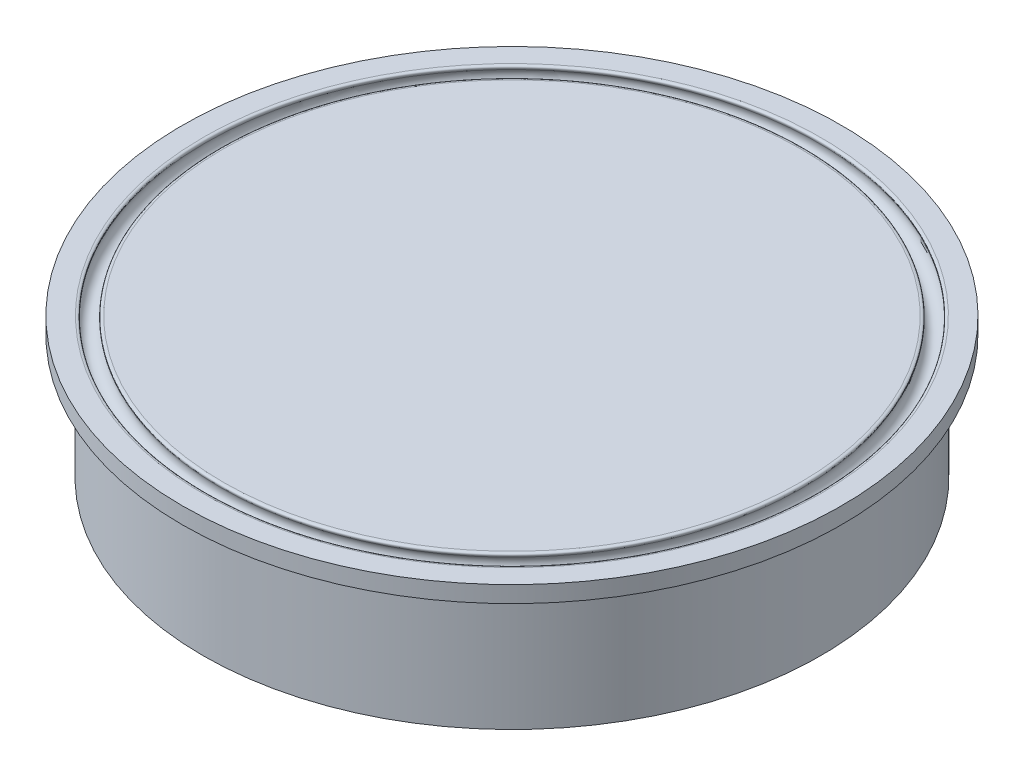
SolidWorks part; units mm, degrees
ref_plane "Alzado" through (0, 0, 0) normal (0, 0, 1) x (1, 0, 0)
ref_plane "Planta" through (0, 0, 0) normal (0, 1, 0) x (1, 0, 0)
ref_plane "Vista lateral" through (0, 0, 0) normal (1, 0, 0) x (0, 0, -1)
sketch "Croquis1" plane through (0, 17, 0) normal (0, 1, 0) x (1, 0, 0)
  circle A3 centre (13.5413, 6.6268) radius 35
  circle A6 centre (13.5413, 6.6268) radius 37.5
extrude "Saliente-Extruir1" add sketch "Croquis1" along normal blind 15
sketch "Croquis2" plane through (0, 32, 0) normal (0, 1, 0) x (1, 0, 0)
  circle A3 centre (13.5413, 6.6268) radius 40
extrude "Saliente-Extruir2" add sketch "Croquis2" along normal blind 2
sketch "Croquis4" plane through (0, 34, 0) normal (0, 1, 0) x (1, 0, 0)
  point P0 (13.5413, 6.6268)
ref_plane "Plano1" through (0, 0, -6.6268) normal (0, 0, 1) x (1, 0, 0)
sketch "Croquis5" plane through (0, 0, -6.6268) normal (0, 0, 1) x (1, 0, 0)
  line L0 (-23.9587, 32) -> (-21.4579, 32) construction
  line L1 (-23.9587, 32) -> (-23.9587, 34) construction
  line L2 (-22.7087, 34) -> (-22.7087, 34.1) construction
  line L3 (53.5413, 34) -> (-26.4587, 34) construction
  line L4 (-23.9587, 34) -> (-22.7087, 34) construction
  line L5 (-22.7087, 31.9) -> (-22.7087, 33) construction
  line L6 (-22.7087, 31.9) -> (-22.7087, 34.1) construction
  circle A0 centre (-22.7087, 33) radius 1.1
ref_plane "Plano2" through (0, 33, 0) normal (0, 1, 0) x (1, 0, 0)
sketch "Croquis6" plane through (0, 33, 0) normal (0, 1, 0) x (1, 0, 0)
  circle A0 centre (13.5413, 6.6268) radius 36.25
sweep "Cortar-Barrer1" cut profiles "Croquis5" path "Croquis6"
fillet "Redondeo1" radius 0.3 2 edges at (13.5413, 34, 30.0815) (13.5413, 34, -42.4185) conic rho 0.5
